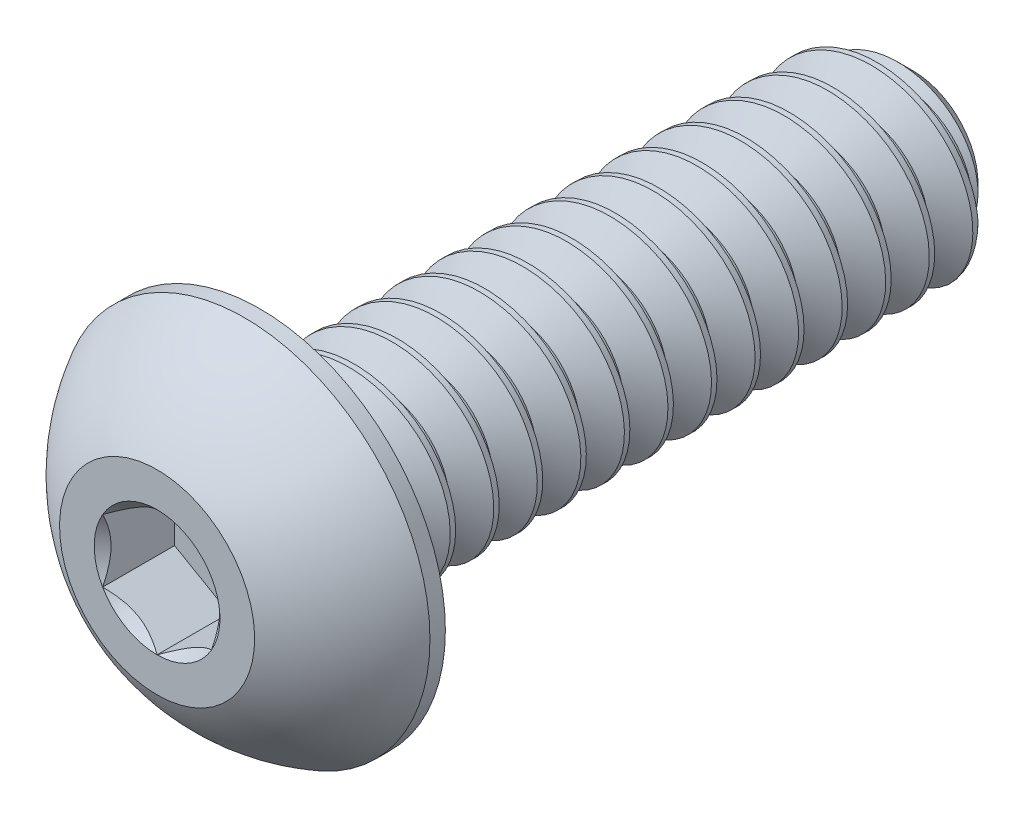
SolidWorks part; units mm, degrees
material "AISI 304"
ref_plane "Front" through (0, 0, 0) normal (0, 0, 1) x (1, 0, 0)
ref_plane "Top" through (0, 0, 0) normal (0, 1, 0) x (1, 0, 0)
ref_plane "Right" through (0, 0, 0) normal (1, 0, 0) x (0, 0, -1)
sketch "Sketch1" plane through (0, 0, 0) normal (1, 0, 0) x (0, 0, -1)
  line L2 (1.4986, 1.4224) -> (11.0236, 1.4224)
  line L3 (11.0236, 1.4224) -> (11.0236, 0)
  line L4 (11.0236, 0) -> (1.4986, 0)
  line L6 (1.2738, 2.7051) -> (1.4986, 2.7051) construction
  line L7 (11.0236, 1.4224) -> (11.0236, -1.4224) construction
  line L8 (0, 0) -> (1.4986, 0) construction
  line L9 (1.4986, 2.7051) -> (1.4986, -2.7051) construction
  line L11 (1.4986, 1.4224) -> (1.4986, 0)
  line L13 (0, 0.7937) -> (0, -0.7937) construction
  line L14 (0, 0.7937) -> (0, 1.4224) construction
  arc A3 (0, 1.4224) -> (1.2738, 2.7051) centre (2.7151, 0) cw construction
  dimension "D1" = 0.2248
revolve "Revolve1" add sketch "Sketch1" angle 360 mid plane about L4
sketch "Sketch3" plane through (0, 0, -11.0236) normal (0, 0, -1) x (-1, 0, 0)
  circle A0 centre (0, 0) radius 1.4224
curve "Helix/Spiral1" pitch 0.635 height 10.16 radius 1.4224 centre (0, 0, -11.0236) axis (0, 0, 1) start towards (0, 1, 0)
sketch "Sketch2" plane through (0, 0, 0) normal (1, 0, 0) x (0, 0, -1)
  line L0 (11.0236, 1.4224) -> (11.5792, 1.4224)
  line L1 (11.5792, 1.4224) -> (11.3411, 1.01)
  line L2 (11.3411, 1.01) -> (11.2617, 1.01)
  line L3 (11.2617, 1.01) -> (11.0236, 1.4224)
  line L4 (11.1427, 1.2162) -> (11.4602, 1.2162) construction
  dimension "D1" = 60
  dimension "D2" = 0.0794
  dimension "D3" = 0.3175
chamfer "Chamfer1" distance 0.4763 angle 45 1 edges at (0, 1.4224, -11.0236)
sweep "Cut-Sweep1" cut profiles "Sketch2" path "Helix/Spiral1" align with end faces yes
sketch "Sketch7" plane through (0, 0, 0) normal (1, 0, 0) x (0, 0, -1)
  line L6 (1.2738, 2.7051) -> (1.4986, 2.7051) construction
  line L8 (0, 0) -> (1.4986, 0) construction
  line L11 (1.4986, 2.7051) -> (1.4986, -2.7051) construction
  line L12 (1.2738, 2.7051) -> (1.4986, 2.7051)
  line L13 (0, 0) -> (1.4986, 0)
  line L14 (0, 0.7937) -> (0, -0.7937) construction
  line L15 (1.4986, 2.7051) -> (1.4986, 0)
  line L16 (0, 1.4224) -> (0, 0)
  arc A2 (1.2738, 2.7051) -> (0, 1.4224) centre (2.7151, 0) ccw construction
  arc A3 (1.2738, 2.7051) -> (0, 1.4224) centre (2.7151, 0) ccw
revolve "Revolve2" add sketch "Sketch7" angle 360 mid plane about L13
sketch "Sketch5" plane through (0, 0, 0) normal (0, 0, 1) x (1, 0, 0)
  line L1 (0.7937, -0.4583) -> (0.7937, 0.4583)
  line L2 (0.7937, 0.4583) -> (0, 0.9165)
  line L3 (0, 0.9165) -> (-0.7937, 0.4583)
  line L4 (-0.7937, 0.4583) -> (-0.7937, -0.4583)
  line L5 (-0.7937, -0.4583) -> (0, -0.9165)
  line L6 (0, -0.9165) -> (0.7937, -0.4583)
  circle A0 centre (0, 0) radius 0.7937 construction
extrude "Cut-Extrude2" cut sketch "Sketch5" against normal blind 1.049
sketch "Sketch6" plane through (0, 0, 0) normal (0, 0, 1) x (1, 0, 0)
  circle A0 centre (0, 0) radius 0.9165
extrude "Cut-Extrude3" cut sketch "Sketch6" against normal blind 1.049 draft 45
sketch "Sketch9" [suppressed] plane through (0, 0, -1.4986) normal (0, 0, 1) x (1, 0, 0)
  circle A2 centre (0, 0) radius 1.4224
extrude "Boss-Extrude2" [suppressed] add sketch "Sketch9" against normal offset from surface (12.7 mm away) 31.75 up to face at (0, 0.9461, -11.0236)
sketch "Sketch10" plane through (0, 0, 0) normal (1, 0, 0) x (0, 0, -1)
  line L0 (11.0236, 1.4224) -> (11.0236, -1.4224) construction
  point P0 (10.0711, -1.4224)
  dimension "D1" = 0.9525
equation "\"D3@Helix/Spiral1\" = \"Lg@Sketch1\" + \"D4@Helix/Spiral1\""
equation "\"D2@Sketch2\" = \"D4@Helix/Spiral1\" * .125"
equation "\"D3@Sketch2\" = \"D4@Helix/Spiral1\" * .5"
equation "\"D1@Chamfer1\" = \"D4@Helix/Spiral1\" * .75"
equation "\"D1@Cut-Extrude2\" = \"Head Ht@Sketch1\" * .7"
equation "\"D1@Sketch1\" = \"Head Ht@Sketch1\" * .15"
equation "\"D1@Sketch10\" = \"D4@Helix/Spiral1\" * 1.5"
equation "\"D1@Cut-Extrude3\" = \"D1@Cut-Extrude2\""
